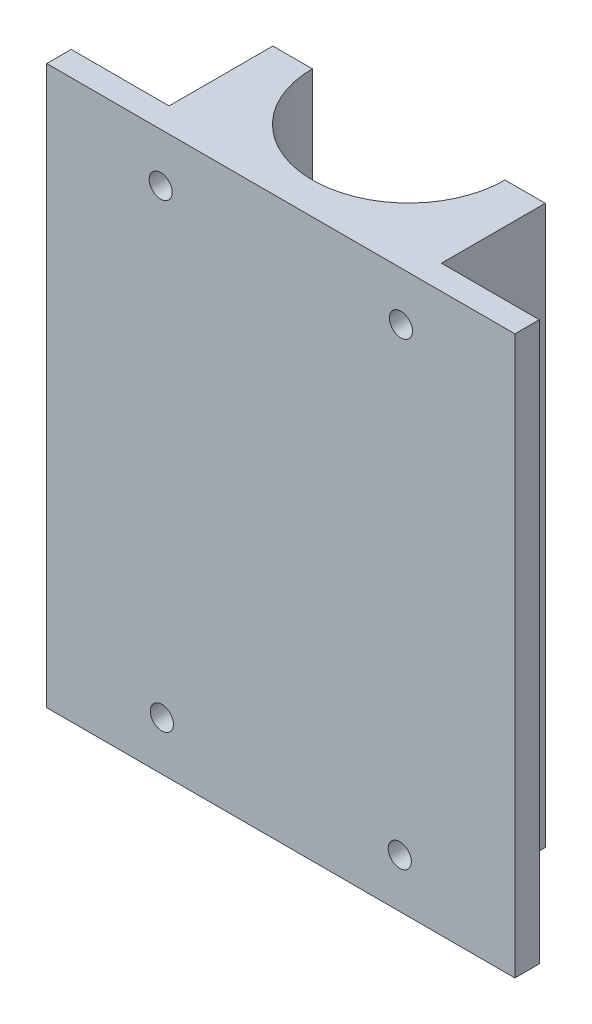
SolidWorks part; units mm, degrees
ref_plane "Front Plane" through (0, 0, 0) normal (0, 0, 1) x (1, 0, 0)
ref_plane "Top Plane" through (0, 0, 0) normal (0, 1, 0) x (1, 0, 0)
ref_plane "Right Plane" through (0, 0, 0) normal (1, 0, 0) x (0, 0, -1)
sketch "Sketch1" plane through (0, 0, 0) normal (0, 1, 0) x (1, 0, 0)
  line L1 (-23.8485, 17.6982) -> (36.9033, 17.6982)
  line L2 (-23.8485, 17.6982) -> (-23.8485, 14.5232)
  line L3 (-23.8485, 14.5232) -> (36.9033, 14.5232)
  line L4 (36.9033, 17.6982) -> (36.9033, 14.5232)
  line L6 (24.2033, 31.1659) -> (-11.1467, 31.1659)
  line L7 (24.2033, 31.1659) -> (24.2033, 17.6982)
  line L8 (24.2033, 17.6982) -> (-11.1467, 17.6982)
  line L9 (-11.1467, 31.1659) -> (-11.1467, 17.6982)
  line L10 (-6.0203, 31.1659) -> (-5.7203, 31.1659)
  line L11 (18.9797, 31.1659) -> (18.6797, 31.1659)
  line L12 (6.5283, 38.6577) -> (6.5283, -0.813) construction
  arc A2 (-6.0203, 31.1659) -> (18.9797, 31.1659) centre (6.4797, 31.1659) ccw
  arc A3 (-5.7203, 31.1659) -> (18.6797, 31.1659) centre (6.4797, 31.1659) ccw
  dimension "D1" = 12.7018
  dimension "D2" = 12.7
extrude "Boss-Extrude3" add sketch "Sketch1" along normal blind 72.39 contours A2 L6 L9 L1 | L12 A2 L1 L2 L3 | L1 L12 L3 L4 | A2 L1 L7 L6 region at (6.5274, 0, -16.1107) region at (-10.7684, 0, -24.432)
extrude "Boss-Extrude4" add sketch "Sketch1<13>" along normal blind 51.39 contours A2 L11 A3 L10
sketch "Sketch1<13>" plane through (0, 0, 0) normal (0, 1, 0) x (1, 0, 0) same geometry as "Sketch1"
hole_wizard "Ø3.0mm Dowel Hole4" positions "Sketch10" profile "Sketch11" hole size "Ø3.0" standard "ANSI Metric" end condition through all
sketch "Sketch10" plane through (0, 0, -31.1659) normal (0, 0, -1) x (-1, 0, 0)
  line L2 (-42.513, 66.04) -> (28.1638, 66.04) construction
  line L4 (-43.5181, 6.35) -> (29.2845, 6.35) construction
  line L6 (-24.2033, 72.39) -> (-24.2033, 0) construction
  line L7 (11.1467, 72.39) -> (11.1467, 0) construction
  line L8 (-24.2033, 72.39) -> (-24.2033, 0) construction
  line L9 (11.1467, 72.39) -> (11.1467, 0) construction
  point P0 (-22.1133, 66.04)
  point P2 (9.0567, 66.04)
  point P4 (8.9067, 6.35)
  point P5 (-21.9633, 6.35)
  dimension "D1" = 2.24
  dimension "D2" = 2.24
  dimension "D3" = 2.09
  dimension "D4" = 2.09
sketch "Sketch11" plane through (22.1133, 66.04, -31.1659) normal (1, 0, 0) x (0, 1, 0)
  line L0 (0, 0) -> (0, 16.6428)
  line L1 (0, 16.6428) -> (1.5, 16.6428)
  line L2 (1.5, 16.6428) -> (1.5, 0)
  line L5 (1.5, 0) -> (0, 0)
  line L11 (0, -6.35) -> (0, 107.95) construction
  dimension "Thru Hole Dia." = 3
  dimension "Thru Hole Depth" = 16.6428
